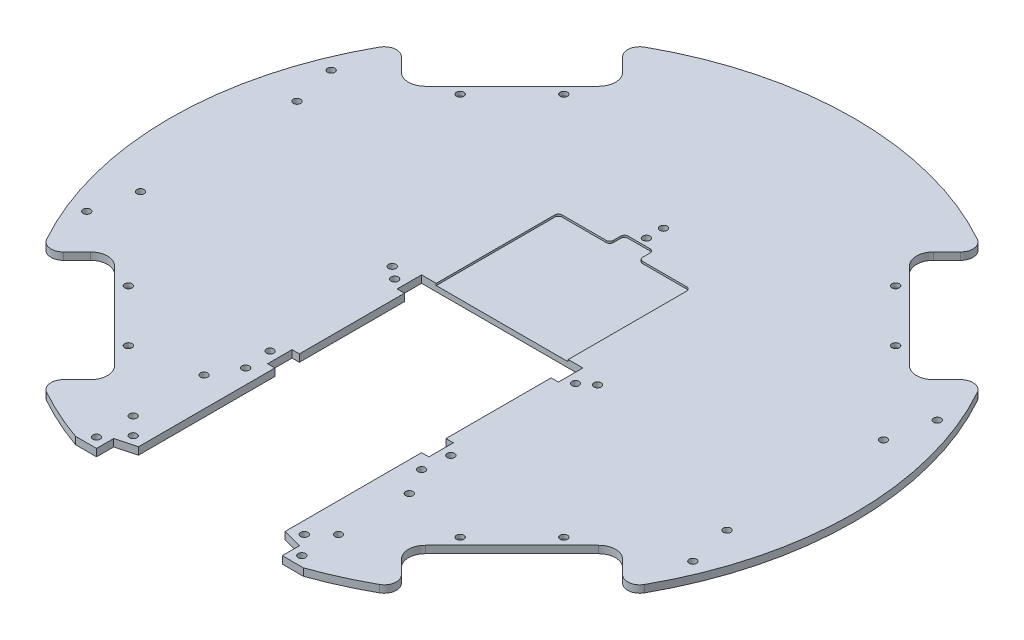
SolidWorks part; units mm, degrees
material "1060 Alloy"
ref_plane "Front Plane" through (0, 0, 0) normal (0, 0, 1) x (1, 0, 0)
ref_plane "Top Plane" through (0, 0, 0) normal (0, 1, 0) x (1, 0, 0)
ref_plane "Right Plane" through (0, 0, 0) normal (1, 0, 0) x (0, 0, -1)
sketch "Sketch1" plane through (0, 0, 0) normal (0, 1, 0) x (1, 0, 0)
  circle A0 centre (0, 0) radius 140
  dimension "D1" = 280
extrude "Boss-Extrude1" add sketch "Sketch1" along normal blind 3
sketch "Sketch7" plane through (0, 3, 0) normal (0, 1, 0) x (1, 0, 0)
  line L0 (-99.0303, -63.6043) -> (-63.6043, -99.0303)
  line L1 (-108.8591, -63.6043) -> (-121.6224, -76.3675)
  line L2 (-63.6043, -108.8591) -> (-76.3675, -121.6224)
  line L3 (-121.6224, -76.3675) -> (-76.3675, -121.6224)
  line L4 (0, 0) -> (-98.9949, -98.9949) construction
  line L7 (0, 0) -> (0, 130) construction
  circle A0 centre (0, 0) radius 140 construction
  arc A1 (-108.8591, -63.6043) -> (-99.0303, -63.6043) centre (-103.9447, -68.5186) cw
  arc A2 (-63.6043, -99.0303) -> (-63.6043, -108.8591) centre (-68.5186, -103.9447) cw
  dimension "D4" = 6.95
  dimension "D1" = 115
  dimension "D2" = 64
  dimension "D3" = 135
extrude "Cut-Extrude4" cut sketch "Sketch7" against normal up to next
sketch "Sketch9" plane through (0, 3, 0) normal (0, 1, 0) x (1, 0, 0)
  line L1 (-63.6043, -99.0303) -> (-99.0303, -63.6043) construction
  line L4 (-108.8591, -63.6043) -> (-119.0017, -73.7469) construction
  circle A0 centre (-89.0955, -67.8823) radius 1.5
  circle A1 centre (-67.8823, -89.0955) radius 1.5
  dimension "D4" = 3
  dimension "D1" = 4
  dimension "D2" = 30
  dimension "D3" = 17
  dimension "D5" = 4
extrude "Cut-Extrude6" cut sketch "Sketch9" against normal up to next
fillet "Fillet1" radius 5 2 edges at (-73.7469, 1.5, 119.0017) (-119.0017, 1.5, 73.7469)
pattern_circular "CirPattern1" count 4 over 360 about axis through (0, 3, 0) along (0, 1, 0) of "Cut-Extrude4", "Fillet1", "Cut-Extrude6"
sketch "Sketch2" plane through (0, 3, 0) normal (0, 1, 0) x (1, 0, 0)
  line L0 (-46.6476, -132) -> (-38, -132)
  line L1 (-30, -122.8564) -> (-30, -67)
  line L2 (-33, -4) -> (33, -4)
  line L3 (30, -67) -> (30, -122.8564)
  line L4 (38, -132) -> (46.6476, -132)
  line L5 (46.6476, -132) -> (46.6476, -140)
  line L6 (46.6476, -140) -> (-46.6476, -140)
  line L7 (-46.6476, -140) -> (-46.6476, -132)
  line L8 (-33, -57) -> (-33, -67)
  line L9 (-33, -67) -> (-30, -67)
  line L10 (33, -57) -> (33, -67)
  line L11 (33, -67) -> (30, -67)
  line L12 (-33, -57) -> (-30, -57)
  line L13 (-30, -57) -> (-30, -14)
  line L14 (-30, -14) -> (-33, -14)
  line L15 (-33, -14) -> (-33, -4)
  line L16 (33, -4) -> (33, -14)
  line L17 (33, -14) -> (30, -14)
  line L18 (30, -14) -> (30, -57)
  line L19 (30, -57) -> (33, -57)
  line L20 (-38, -132) -> (-38, -125)
  line L21 (-38, -125) -> (-30, -122.8564)
  line L22 (38, -132) -> (38, -125)
  line L23 (38, -125) -> (30, -122.8564)
  circle A0 centre (0, 0) radius 140 construction
  dimension "D8" = 3
  dimension "D5" = 63
  dimension "D6" = 66
  dimension "D1" = 8
  dimension "D2" = 65
  dimension "D3" = 60
  dimension "D4" = 16.6476
  dimension "D7" = 10
  dimension "D9" = 76
  dimension "D10" = 7
  dimension "D11" = 105
extrude "Cut-Extrude1" cut sketch "Sketch2" against normal up to next
fillet "Fillet3" radius 1.5 8 edges at (67.8823, 0, 90.5955) (89.0955, 0, 69.3823) (89.0955, 0, -66.3823) (67.8823, 0, -87.5955) (-67.8823, 0, -87.5955) (-89.0955, 0, -66.3823) (-67.8823, 0, 90.5955) (-89.0955, 0, 69.3823)
sketch "Sketch10" plane through (0, 3, 0) normal (0, 1, 0) x (1, 0, 0)
  line L0 (-33, -57) -> (-33, -67) construction
  line L1 (33, -67) -> (33, -57) construction
  line L2 (-33, -67) -> (-30, -67) construction
  line L4 (-30, -14) -> (-33, -14) construction
  line L5 (33, -4) -> (-33, -4) construction
  circle A0 centre (-37, -62) radius 1.5
  circle A1 centre (37, -62) radius 1.5
  circle A2 centre (-37, -11) radius 1.5
  circle A3 centre (37, -11) radius 1.5
  circle A4 centre (-42, -7) radius 1.5
  circle A5 centre (42, -7) radius 1.5
  point P17 (-31.5, -14)
  dimension "D3" = 3
  dimension "D1" = 4
  dimension "D2" = 4
  dimension "D4" = 5
  dimension "D5" = 3
  dimension "D6" = 3
  dimension "D7" = 5
  dimension "D8" = 5
extrude "Cut-Extrude7" cut sketch "Sketch10" against normal up to next
sketch "Sketch13" plane through (0, 3, 0) normal (0, 1, 0) x (1, 0, 0)
  line L0 (-38, -132) -> (-46.6476, -132) construction
  line L1 (-38, -132) -> (-46.6476, -132) construction
  circle A0 centre (-42, -84) radius 1.5
  circle A1 centre (-42, -113) radius 1.5
  circle A2 centre (42, -113) radius 1.5
  circle A3 centre (42, -84) radius 1.5
  dimension "D1" = 3
  dimension "D2" = 19
  dimension "D3" = 48
  dimension "D4" = 42
  dimension "D5" = 42
extrude "Cut-Extrude9" cut sketch "Sketch13" against normal up to next
sketch "Sketch16" plane through (0, 3, 0) normal (0, 1, 0) x (1, 0, 0)
  circle A0 centre (0, 62) radius 1.5
  circle A4 centre (0, 55) radius 1.5
  dimension "D2" = 3
  dimension "D5" = 3
  dimension "D1" = 62
  dimension "D7" = 55
extrude "Cut-Extrude12" cut sketch "Sketch16" against normal up to next
sketch "Sketch17" plane through (0, 3, 0) normal (0, 1, 0) x (1, 0, 0)
  circle A0 centre (-124, 50) radius 1.5
  circle A1 centre (-124, -50) radius 1.5
  circle A2 centre (124, 50) radius 1.5
  circle A3 centre (124, -50) radius 1.5
  dimension "D1" = 3
  dimension "D2" = 50
  dimension "D3" = 50
  dimension "D4" = 124
  dimension "D5" = 124
extrude "Cut-Extrude13" cut sketch "Sketch17" against normal up to next
sketch "Sketch18" plane through (0, 3, 0) normal (0, 1, 0) x (1, 0, 0)
  line L1 (-27, -4) -> (27, -4)
  line L2 (-27, -4) -> (-27, 46)
  line L3 (-27, 46) -> (27, 46)
  line L4 (27, -4) -> (27, 46)
  line L5 (33, -4) -> (-33, -4) construction
  dimension "D1" = 50
  dimension "D2" = 54
  dimension "D3" = 27
extrude "Cut-Extrude14" cut sketch "Sketch18" against normal blind 0.8
sketch "Sketch19" plane through (0, 3, 0) normal (0, 1, 0) x (1, 0, 0)
  line L0 (-38, -125) -> (-38, -132) construction
  line L1 (-38, -132) -> (-46.6476, -132) construction
  line L2 (38, -132) -> (38, -125) construction
  circle A0 centre (-42, -128) radius 1.5
  circle A1 centre (42, -128) radius 1.5
  dimension "D4" = 3
  dimension "D1" = 4
  dimension "D2" = 4
  dimension "D3" = 4
extrude "Cut-Extrude15" cut sketch "Sketch19" against normal up to next
sketch "Sketch20" plane through (0, 3, 0) normal (0, 1, 0) x (1, 0, 0)
  line L0 (27, 46) -> (-27, 46) construction
  line L1 (-6, 46) -> (6, 46)
  line L2 (-6, 46) -> (-6, 52)
  line L3 (-6, 52) -> (6, 52)
  line L4 (6, 46) -> (6, 52)
  circle A0 centre (0, 55) radius 1.5 construction
  dimension "D1" = 12
  dimension "D2" = 6
  dimension "D3" = 3
extrude "Cut-Extrude16" cut sketch "Sketch20" against normal up to surface (0.8 mm away) up to face at (0, 2.2, -21)
fillet "Fillet4" radius 1.5 6 edges at (6, 2.6, -46) (27, 2.6, -46) (-27, 2.6, -46) (-6, 2.6, -46) (6, 2.6, -52) (-6, 2.6, -52)
sketch "Sketch21" plane through (0, 3, 0) normal (0, 1, 0) x (1, 0, 0)
  circle A0 centre (-35, -120) radius 1.5
  circle A1 centre (-36, -73) radius 1.5
  circle A2 centre (35, -120) radius 1.5
  circle A3 centre (36, -73) radius 1.5
  circle A4 centre (-42, -128) radius 1.5 construction
  circle A5 centre (42, -128) radius 1.5 construction
  dimension "D1" = 7
  dimension "D3" = 3
  dimension "D2" = 8
  dimension "D4" = 47
  dimension "D5" = 1
  dimension "D6" = 1
  dimension "D7" = 7
extrude "Cut-Extrude17" cut sketch "Sketch21" against normal up to next
sketch "Sketch22" plane through (0, 3, 0) normal (0, 1, 0) x (1, 0, 0)
  circle A0 centre (120, 32) radius 1.5
  circle A1 centre (120, -32) radius 1.5
  circle A2 centre (-120, 32) radius 1.5
  circle A3 centre (-120, -32) radius 1.5
  dimension "D1" = 3
  dimension "D2" = 120
  dimension "D3" = 32
  dimension "D4" = 32
  dimension "D5" = 120
extrude "Cut-Extrude18" cut sketch "Sketch22" against normal up to next
